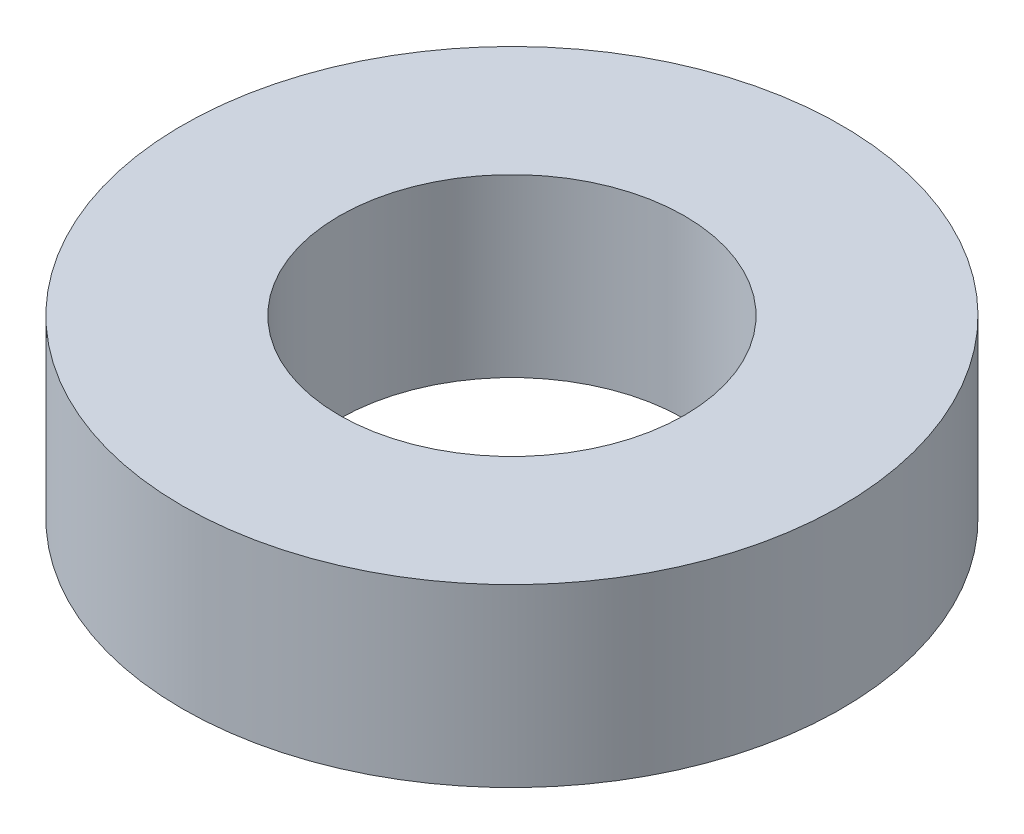
SolidWorks part; units mm, degrees
ref_plane "Front Plane" through (0, 0, 0) normal (0, 0, 1) x (1, 0, 0)
ref_plane "Top Plane" through (0, 0, 0) normal (0, 1, 0) x (1, 0, 0)
ref_plane "Right Plane" through (0, 0, 0) normal (1, 0, 0) x (0, 0, -1)
sketch "Sketch1" plane through (0, 0, 0) normal (0, 1, 0) x (1, 0, 0)
  circle A0 centre (0, 0) radius 52.5
  dimension "FLANGE_OD" = 105
extrude "Boss-Extrude1" add sketch "Sketch1" along normal blind 28
sketch "Sketch2" plane through (0, 0, 0) normal (0, 1, 0) x (1, 0, 0)
  circle A0 centre (0, 0) radius 27.5
  dimension "BORE_D" = 55
extrude "Cut-Extrude1" cut sketch "Sketch2" along normal through all
sketch "Sketch3" plane through (0, 28, 0) normal (0, 1, 0) x (1, 0, 0)
  circle A0 centre (0, 0) radius 21.1548 construction
  circle A1 centre (-21.1548, 0) radius 3.1111
  dimension "BOLT_D" = 6.2223
  dimension "BOLT_PCD" = 42.3096
extrude "Cut-Extrude2" cut sketch "Sketch3" against normal blind 17.9407 rebuild error yes
pattern_circular "CirPattern1" count 6 over 360 rebuild error yes
